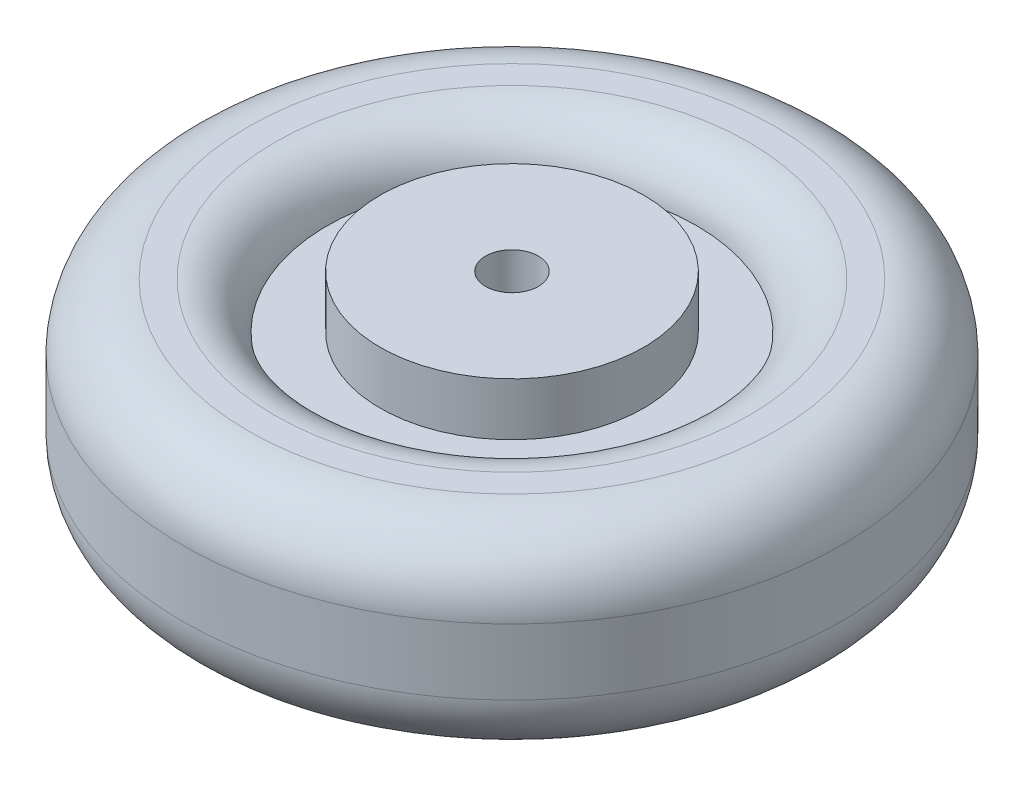
SolidWorks part; units mm, degrees
ref_plane "Plan de face" through (0, 0, 0) normal (0, 0, 1) x (1, 0, 0)
ref_plane "Plan de dessus" through (0, 0, 0) normal (0, 1, 0) x (1, 0, 0)
ref_plane "Plan de droite" through (0, 0, 0) normal (1, 0, 0) x (0, 0, -1)
sketch "Esquisse1" plane through (0, 0, 0) normal (0, 0, 1) x (1, 0, 0)
  line L0 (0, 0) -> (0, 20.5) construction
  line L1 (-4, -16) -> (-4, 16)
  line L2 (-4, 16) -> (-20, 16)
  line L3 (-20, 16) -> (-20, 8)
  line L4 (-20, 8) -> (-28, 8)
  line L5 (-28, 8) -> (-28, 15)
  line L6 (-28, 15) -> (-50, 15)
  line L7 (-50, 15) -> (-50, -15)
  line L8 (-50, 0) -> (-4, 0) construction
  line L9 (-28, -15) -> (-50, -15)
  line L10 (-28, -8) -> (-28, -15)
  line L11 (-20, -8) -> (-28, -8)
  line L12 (-20, -16) -> (-20, -8)
  line L13 (-4, -16) -> (-20, -16)
  dimension "D1" = 40
  dimension "D2" = 8
  dimension "D3" = 56
  dimension "D4" = 100
  dimension "D5" = 30
  dimension "D6" = 32
  dimension "D7" = 8
revolve "Révolution1" add sketch "Esquisse1" angle 360 about L0
fillet "Congé1" radius 10 2 edges at (0, 15, -50) (0, -15, -50)
fillet "Congé2" radius 8 2 edges at (0, -15, -28) (0, 15, -28)
